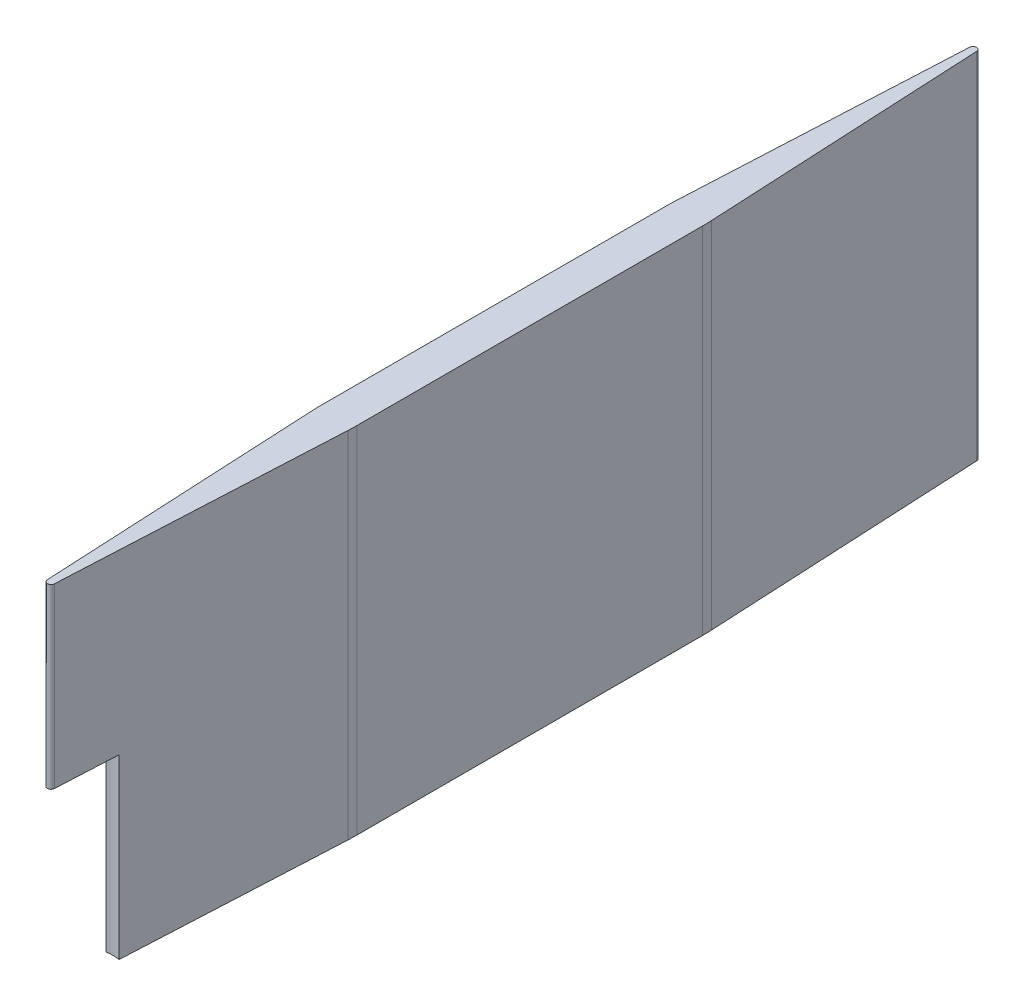
SolidWorks part; units mm, degrees
ref_plane "Front Plane" through (0, 0, 0) normal (0, 0, 1) x (1, 0, 0)
ref_plane "Top Plane" through (0, 0, 0) normal (0, 1, 0) x (1, 0, 0)
ref_plane "Right Plane" through (0, 0, 0) normal (1, 0, 0) x (0, 0, -1)
sketch "Sketch1" plane through (0, 0, 0) normal (0, 1, 0) x (1, 0, 0)
  line L0 (0, 0) -> (0, 76.2) construction
  line L1 (-1.27, 50.8) -> (-1.27, 25.4)
  line L2 (-1.27, 25.4) -> (-0.2537, 5.0737)
  line L3 (-1.27, 50.8) -> (-0.2537, 71.1263)
  line L4 (1.27, 25.4) -> (0.2537, 5.0737)
  line L5 (1.27, 50.8) -> (0.2537, 71.1263)
  line L6 (1.27, 50.8) -> (1.27, 25.4)
  arc A0 (-0.2537, 71.1263) -> (0.2537, 71.1263) centre (0, 71.1137) cw
  arc A1 (-0.2537, 5.0737) -> (0.2537, 5.0737) centre (0, 5.0863) ccw
  dimension "D5" = 0.254
  dimension "D1" = 25.4
  dimension "D2" = 76.2
  dimension "D3" = 25.4
  dimension "D4" = 1.27
extrude "Boss-Extrude1" add sketch "Sketch1" along normal blind 25.4
fillet "Fillet1" radius 12.7 4 edges at (-1.27, 12.7, -25.4) (-1.27, 12.7, -50.8) (1.27, 12.7, -25.4) (1.27, 12.7, -50.8)
sketch "Sketch3" plane through (0, 0, 0) normal (0, 0, 1) x (1, 0, 0)
  line L0 (0, 0) -> (0, 1.5875) construction
  circle A0 centre (0, 1.5875) radius 1.5875
  dimension "D1" = 3.175
  dimension "D2" = 1.5875
extrude "Boss-Extrude2" [suppressed] add sketch "Sketch3" along normal blind 76.2 and the other way blind 31.75
fillet "Fillet2" [suppressed] radius 6.35
sketch "Sketch4" plane through (0, 0, 0) normal (0, 1, 0) x (1, 0, 0)
  line L0 (0, 0) -> (0, 6.35) construction
  line L1 (-3.4925, 0) -> (3.4925, 0) construction
  circle A0 centre (0, 6.35) radius 3.175
  dimension "D1" = 6.35
  dimension "D2" = 6.35
extrude "Cut-Extrude2" cut sketch "Sketch4" along normal blind 12.7
